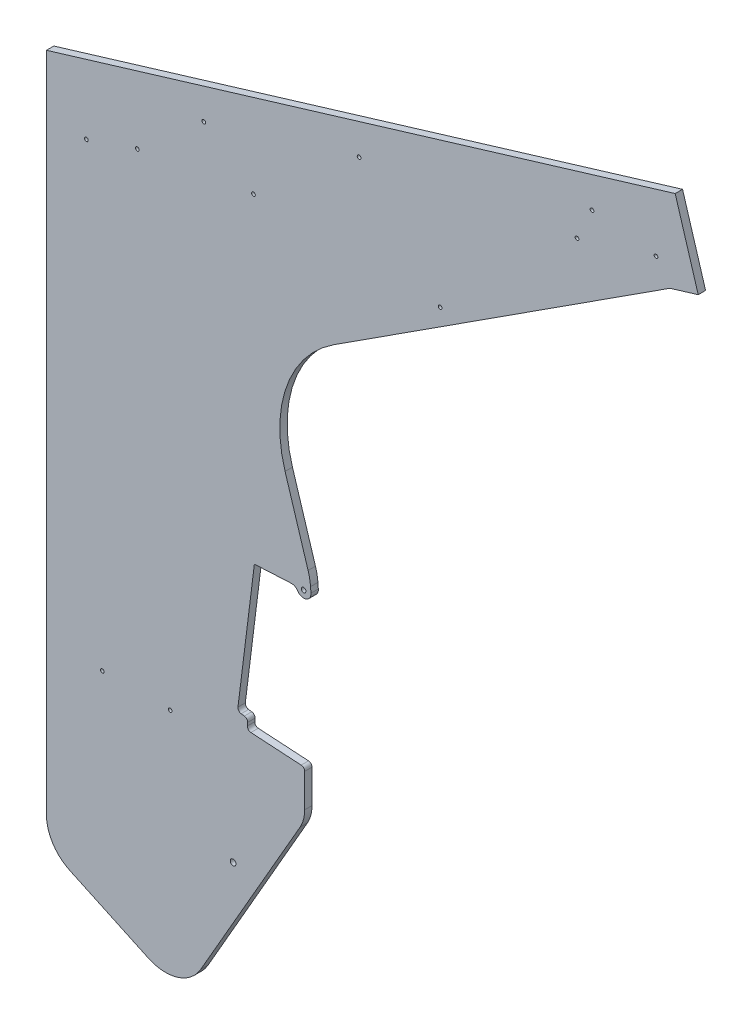
SolidWorks part; units mm, degrees
material "Beech"
ref_plane "Front Plane" through (0, 0, 0) normal (0, 0, 1) x (1, 0, 0)
ref_plane "Top Plane" through (0, 0, 0) normal (0, 1, 0) x (1, 0, 0)
ref_plane "Right Plane" through (0, 0, 0) normal (1, 0, 0) x (0, 0, -1)
sketch "Sketch1" plane through (0, 0, 0) normal (0, 0, 1) x (1, 0, 0)
  line L7 (105.0266, 156.03) -> (398.6241, 345.5216)
  line L8 (398.6241, 345.5216) -> (422.935, 352.8794)
  line L9 (422.935, 352.8794) -> (403.0991, 418.4193)
  line L10 (403.0991, 418.4193) -> (-138.3789, 254.5381)
  line L11 (-138.3789, 254.5381) -> (-138.3789, -315.4534)
  line L12 (-118.2139, -347.1062) -> (-48.0382, -379.8296)
  line L13 (1.5139, -351.2208) -> (35.9297, 42.1538)
  line L14 (109.0999, 158.659) -> (398.6241, 345.5216)
  line L15 (398.6241, 345.5216) -> (422.935, 352.8794)
  line L16 (422.935, 352.8794) -> (403.0991, 418.4193)
  line L17 (403.0991, 418.4193) -> (-138.3789, 254.5381)
  line L18 (-138.3789, 254.5381) -> (-138.3789, -315.4534)
  line L19 (-118.2139, -347.1062) -> (-50.5059, -378.6789)
  line L21 (-5.4671, -364.4315) -> (80.009, -215.7351)
  line L22 (84, -200.7842) -> (84, -156.3804)
  line L23 (84, -156.3804) -> (45.8908, -155.3854)
  line L24 (45.8908, -155.3854) -> (48.6774, -48.6606)
  line L25 (48.6774, -48.6606) -> (90.1605, -46.0697)
  line L26 (90.1605, -46.0697) -> (89.0709, -31.7487)
  line L27 (86.9733, -20.7388) -> (67.1502, 43.2142)
  arc A2 (80.009, -215.7351) -> (84, -200.7842) centre (54, -200.7842) ccw
  arc A3 (105.0266, 156.03) -> (35.9297, 42.1538) centre (187.6695, 27.9835) ccw
  arc A4 (-138.3789, -315.4534) -> (-118.2139, -347.1062) centre (-103.4539, -315.4534) ccw
  arc A5 (-48.0382, -379.8296) -> (1.5139, -351.2208) centre (-33.2782, -348.1768) ccw
  arc A7 (-138.3789, -315.4534) -> (-118.2139, -347.1062) centre (-103.4539, -315.4534) ccw
  arc A9 (89.0709, -31.7487) -> (86.9733, -20.7388) centre (39.215, -35.5422) ccw
  arc A10 (109.0999, 158.659) -> (67.1502, 43.2142) centre (164.1952, 73.2946) ccw
  arc A11 (-50.5059, -378.6789) -> (-5.4671, -364.4315) centre (-35.746, -347.0261) ccw
  dimension "D2" = 101.6
  dimension "D3" = 34.925
  dimension "D1" = 0
extrude "Boss-Extrude1" add sketch "Sketch1" along normal blind 6.35
sketch "Sketch2" plane through (0, 0, 6.35) normal (0, 0, 1) x (1, 0, 0)
  circle A1 centre (83.098, -37.255) radius 2
extrude "Cut-Extrude1" cut sketch "Sketch2" against normal through all
sketch "Sketch3" plane through (0, 0, 6.35) normal (0, 0, 1) x (1, 0, 0)
  line L0 (84, -156.3804) -> (45.8908, -155.3854) construction
  line L1 (45.8908, -155.3854) -> (48.6774, -48.6606) construction
  line L2 (48.6774, -48.6606) -> (90.1605, -46.0697) construction
  line L3 (34.5371, -166.0421) -> (35.0858, -157.1104)
  line L4 (35.0858, -157.1104) -> (26.1865, -156.0047)
  line L5 (84, -169.0804) -> (84, -156.3804)
  line L6 (84, -156.3804) -> (45.8908, -155.3854)
  line L7 (45.8908, -155.3854) -> (48.6774, -48.6606)
  line L8 (48.6774, -48.6606) -> (90.1605, -46.0697)
  line L9 (90.1605, -46.0697) -> (89.9196, -42.9035)
  line L10 (89.9196, -42.9035) -> (77.2443, -43.6952)
  line L11 (77.2443, -43.6952) -> (76.92, -37.3323)
  line L12 (76.92, -37.3323) -> (40.7015, -39.1783)
  line L13 (40.7015, -39.1783) -> (26.1865, -156.0047)
  line L14 (34.5371, -166.0421) -> (84, -169.0804)
  dimension "D1" = 12.7
  dimension "D2" = 3.175
  dimension "D3" = 12.7
extrude "Cut-Extrude2" cut sketch "Sketch3" against normal up to next
fillet "Fillet4" radius 6.35 2 edges at (77.2443, -43.6952, 3.175) (89.9196, -42.9035, 3.175)
fillet "Fillet5" radius 6.35 1 edges at (76.92, -37.3323, 3.175)
fillet "Fillet6" radius 3.175 4 edges at (84, -169.0804, 3.175) (34.5371, -166.0421, 3.175) (35.0858, -157.1104, 3.175) (26.1865, -156.0047, 3.175)
hole_wizard "#8 Clearance Hole1" positions "Sketch4" profile "Sketch5" hole size "#8" standard "ANSI Inch" end condition through all
sketch "Sketch4" plane through (0, 0, 0) normal (0, 0, -1) x (-1, 0, 0)
  circle A0 centre (-22.4173, -270.7692) radius 2.4574 construction
  point P1 (-22.4173, -270.7692)
sketch "Sketch5" plane through (22.4173, -270.7692, 0) normal (1, 0, 0) x (0, 1, 0)
  line L0 (0, 0) -> (0, 6.35)
  line L1 (0, 6.35) -> (2.4574, 6.35)
  line L2 (2.4574, 6.35) -> (2.4574, 0)
  line L5 (2.4574, 0) -> (0, 0)
  line L11 (0, -6.35) -> (0, 107.95) construction
  dimension "Thru Hole Dia." = 4.9149
  dimension "Thru Hole Depth" = 6.35
hole_wizard "Hole1" positions "Sketch6" profile "Sketch7" legacy
sketch "Sketch6" plane through (-277.2867, -215.2871, 12.7) normal (0, 0, 1) x (-0.09, -0.9959, 0)
  point P4 (-507.0387, 229.7761)
  point P6 (-559.3712, 359.3037)
  point P8 (-637.87, 553.5951)
  point P10 (-636.0712, 609.1114)
  point P12 (-609.4494, 543.2202)
  point P14 (-488.8705, 435.7568)
  point P16 (-478.4144, 275.2927)
  point P18 (-453.1036, 177.1887)
  point P20 (-434.4591, 134.8062)
  point P22 (-52.9605, 241.7526)
  point P24 (-47.6978, 183.4898)
sketch "Sketch7" plane through (-2.8292, 269.0251, 12.7) normal (1, 0, 0) x (0, -1, 0)
  line L0 (0, 0) -> (0, 32.7039)
  line L1 (0, 32.7039) -> (1.5875, 31.75)
  line L2 (1.5875, 31.75) -> (1.5875, 4.0177)
  line L3 (1.5875, 4.0177) -> (5.08, 0)
  line L4 (5.08, 0) -> (0, 0)
  line L5 (0, -14.3089) -> (0, 102.4216) construction
  line L6 (0, 32.7039) -> (-1.5875, 31.75) construction
  line L7 (-1.5875, 4.0177) -> (-5.08, 0) construction
  dimension "Diameter" = 3.175
  dimension "Depth" = 31.75
  dimension "C-Sink Diameter" = 10.16
  dimension "C-Sink Angle" = 82
  dimension "Drill Angle" = 118
